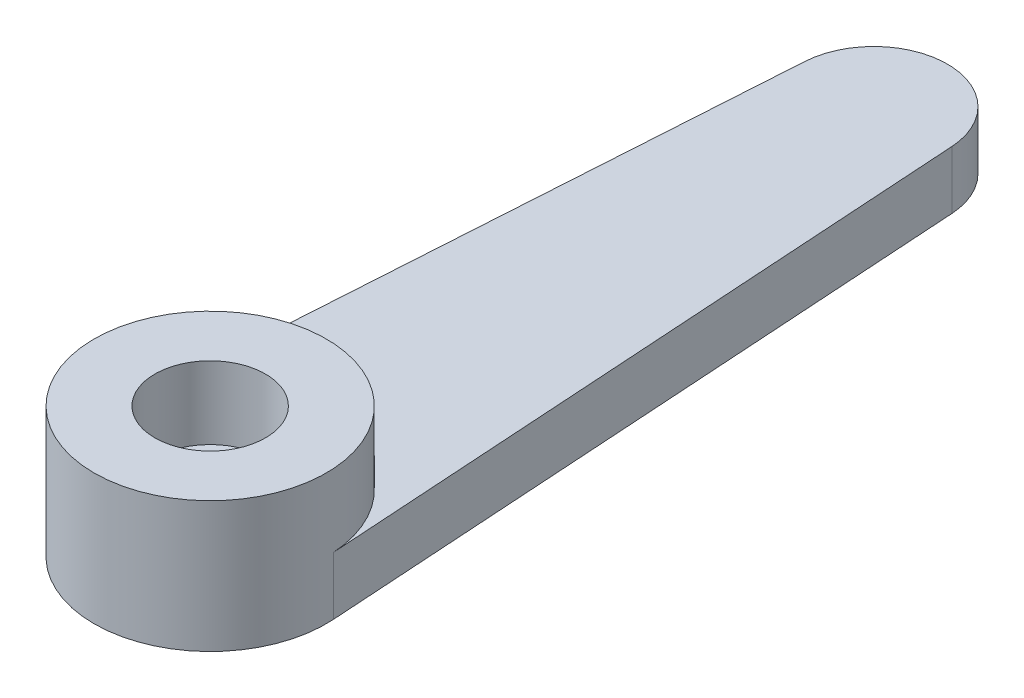
SolidWorks part; units mm, degrees
ref_plane "Front Plane" through (0, 0, 0) normal (0, 0, 1) x (1, 0, 0)
ref_plane "Top Plane" through (0, 0, 0) normal (0, 1, 0) x (1, 0, 0)
ref_plane "Right Plane" through (0, 0, 0) normal (1, 0, 0) x (0, 0, -1)
sketch "Sketch1" plane through (0, 0, 0) normal (0, 1, 0) x (1, 0, 0)
  line L0 (0, 0) -> (0, 25.4) construction
  line L1 (-2.5348, 23.0222) -> (-3.9918, 0.2555)
  line L2 (2.5348, 23.0222) -> (3.9918, 0.2555)
  circle A0 centre (0, 0) radius 4
  circle A1 centre (0, 22.86) radius 2.54
  dimension "D1" = 8
  dimension "D3" = 5.08
  dimension "D2" = 25.4
extrude "Boss-Extrude1" add sketch "Sketch1" along normal blind 2 contours A0 L0 A1 L1 | L0 A0 L2 A1 | A1 L0 | L0 A1 | A0 region at (-1.7105, 0, -11.5373) region at (1.7105, 0, -11.5373) region at (2.6592, 0, -2.8348) region at (-1.078, 0, -22.86) region at (1.078, 0, -22.86)
sketch "Sketch2" plane through (0, 2, 0) normal (0, 1, 0) x (1, 0, 0)
  circle A0 centre (0, 0) radius 4
  circle A1 centre (0, 0) radius 1.9064
extrude "Boss-Extrude2" add sketch "Sketch2" along normal blind 2.5
sketch "Sketch3" plane through (0, 0, 0) normal (0, -1, 0) x (1, 0, 0)
  line L0 (0, 0) -> (0, -25.4) construction
  arc A0 (-2.5348, -23.0222) -> (2.5348, -23.0222) centre (0, -22.86) ccw construction
